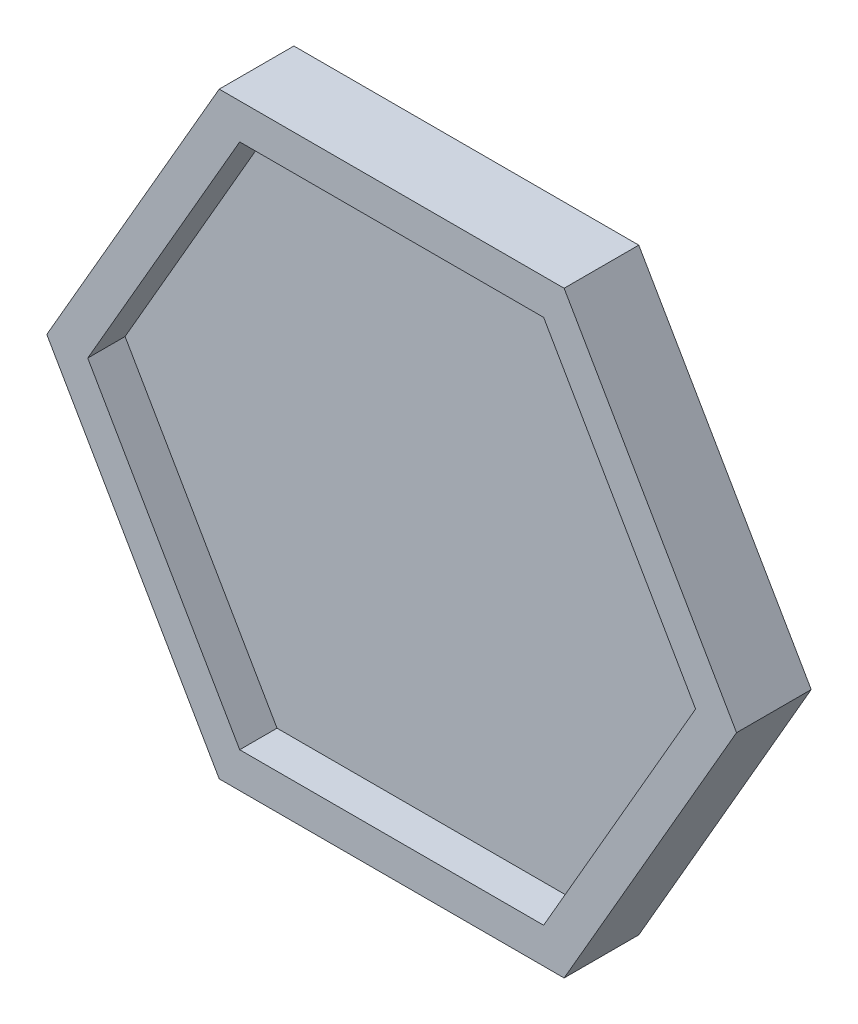
SolidWorks part; units mm, degrees
note: The reader was unsure of these and kept them because the rebuilt part matched: shared geometry of "Sketch5<2>".
ref_plane "Front" through (0, 0, 0) normal (0, 0, 1) x (1, 0, 0)
ref_plane "Top" through (0, 0, 0) normal (0, 1, 0) x (1, 0, 0)
ref_plane "Right" through (0, 0, 0) normal (1, 0, 0) x (0, 0, -1)
sketch "Sketch1" plane through (0, 0, 0) normal (0, 0, 1) x (1, 0, 0)
  line L1 (5.889, 0) -> (2.9445, 5.1)
  line L2 (2.9445, 5.1) -> (-2.9445, 5.1)
  line L3 (-2.9445, 5.1) -> (-5.889, 0)
  line L4 (-5.889, 0) -> (-2.9445, -5.1)
  line L5 (-2.9445, -5.1) -> (2.9445, -5.1)
  line L6 (2.9445, -5.1) -> (5.889, 0)
  line L7 (8.0829, 0) -> (4.0415, 7)
  line L8 (4.0415, 7) -> (-4.0415, 7)
  line L9 (-4.0415, 7) -> (-8.0829, 0)
  line L10 (-8.0829, 0) -> (-4.0415, -7)
  line L11 (-4.0415, -7) -> (4.0415, -7)
  line L12 (4.0415, -7) -> (8.0829, 0)
  circle A0 centre (0, 0) radius 5.1 construction
  circle A1 centre (0, 0) radius 7 construction
extrude "Boss-Extrude1" add sketch "Sketch1" along normal blind 1 and the other way blind 2.5
sketch "Sketch3" plane through (0, 0, 0) normal (0, 0, 1) x (1, 0, 0)
  line L0 (-5.889, 0) -> (-2.9445, -5.1) construction
  line L7 (5.5426, 0) -> (2.7713, 4.8)
  line L8 (2.7713, 4.8) -> (-2.7713, 4.8)
  line L9 (-2.7713, 4.8) -> (-5.5426, 0)
  line L10 (-5.5426, 0) -> (-2.7713, -4.8)
  line L11 (-2.7713, -4.8) -> (2.7713, -4.8)
  line L12 (2.7713, -4.8) -> (5.5426, 0)
  line L13 (5.889, 0) -> (2.9445, 5.1)
  line L14 (2.9445, 5.1) -> (-2.9445, 5.1)
  line L15 (-2.9445, 5.1) -> (-5.889, 0)
  line L16 (-5.889, 0) -> (-2.9445, -5.1)
  line L17 (-2.9445, -5.1) -> (2.9445, -5.1)
  line L18 (2.9445, -5.1) -> (5.889, 0)
  circle A0 centre (0, 0) radius 4.8 construction
  circle A1 centre (0, 0) radius 5.1 construction
extrude "Boss-Extrude2" add sketch "Sketch3" against normal up to surface (2.5 mm away) up to face at (0, 0, -2.5)
sketch "Sketch4" plane through (0, 0, -2.5) normal (0, 0, -1) x (-1, 0, 0)
  line L1 (9.2376, 0) -> (4.6188, 8)
  line L2 (4.6188, 8) -> (-4.6188, 8)
  line L3 (-4.6188, 8) -> (-9.2376, 0)
  line L4 (-9.2376, 0) -> (-4.6188, -8)
  line L5 (-4.6188, -8) -> (4.6188, -8)
  line L6 (4.6188, -8) -> (9.2376, 0)
  circle A0 centre (0, 0) radius 8 construction
extrude "Boss-Extrude3" add sketch "Sketch4" along normal blind 1
sketch "Sketch5" plane through (0, 0, -2.5) normal (0, 0, 1) x (1, 0, 0)
  line L1 (-4.0703, 7.05) -> (-8.1406, 0)
  line L2 (-8.1406, 0) -> (-4.0703, -7.05)
  line L3 (-4.0703, -7.05) -> (4.0703, -7.05)
  line L4 (4.0703, -7.05) -> (8.1406, 0)
  line L5 (8.1406, 0) -> (4.0703, 7.05)
  line L6 (4.0703, 7.05) -> (-4.0703, 7.05)
  line L7 (-4.6188, 8) -> (-9.2376, 0)
  line L8 (-9.2376, 0) -> (-4.6188, -8)
  line L9 (-4.6188, -8) -> (4.6188, -8)
  line L10 (4.6188, -8) -> (9.2376, 0)
  line L11 (9.2376, 0) -> (4.6188, 8)
  line L12 (4.6188, 8) -> (-4.6188, 8)
  circle A0 centre (0, 0) radius 7.05 construction
  circle A1 centre (0, 0) radius 8 construction
extrude "Boss-Extrude4" add sketch "Sketch5" along normal blind 1
extrude "Cut-Extrude1" cut sketch "Sketch5<2>" along normal through all
sketch "Sketch5<2>" plane through (0, 0, -2.5) normal (0, 0, 1) x (1, 0, 0) same geometry as "Sketch5"
